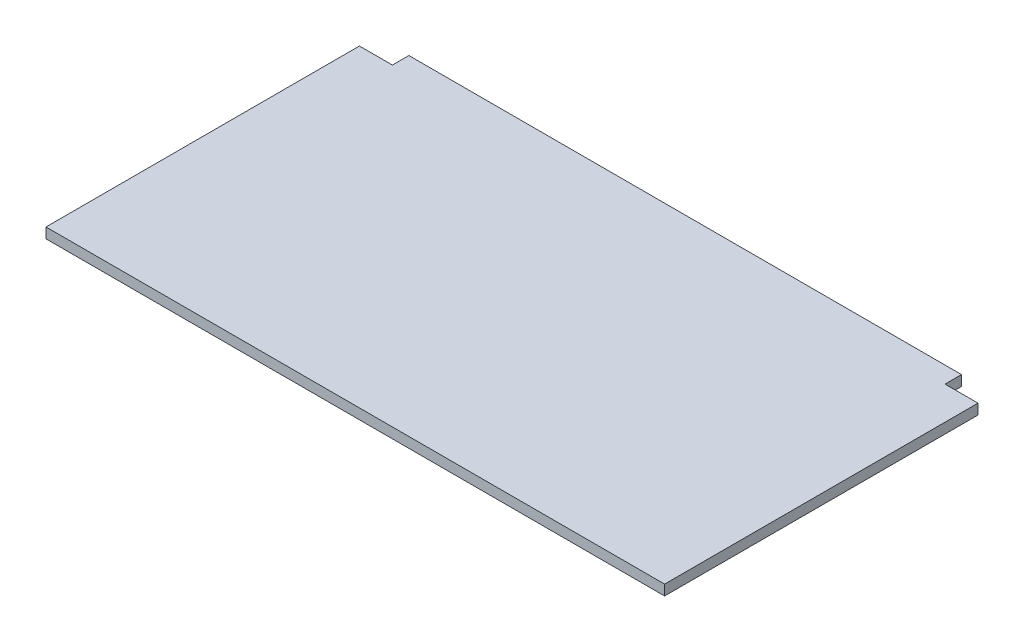
SolidWorks part; units mm, degrees
material "Cedar"
ref_plane "Front Plane" through (0, 0, 0) normal (0, 0, 1) x (1, 0, 0)
ref_plane "Top Plane" through (0, 0, 0) normal (0, 1, 0) x (1, 0, 0)
ref_plane "Right Plane" through (0, 0, 0) normal (1, 0, 0) x (0, 0, -1)
sketch "Sketch1" plane through (0, 0, 0) normal (0, 1, 0) x (1, 0, 0)
  line L1 (750, -400) -> (-750, -400)
  line L2 (750, -400) -> (750, 400)
  line L3 (750, 400) -> (-750, 400)
  line L4 (-750, -400) -> (-750, 400)
  line L5 (750, -400) -> (-750, 400) construction
  line L6 (750, 400) -> (-750, -400) construction
  point P0 (0, 0)
  dimension "D1" = 800
  dimension "D2" = 1500
extrude "Boss-Extrude1" add sketch "Sketch1" along normal blind 25
sketch "Sketch2" plane through (0, 25, 0) normal (0, 1, 0) x (1, 0, 0)
  line L0 (750, 400) -> (-750, 400) construction
  line L1 (-761.4719, 427.6992) -> (-670, 427.6992)
  line L2 (-761.4719, 427.6992) -> (-761.4719, 360)
  line L3 (-761.4719, 360) -> (-670, 360)
  line L4 (-670, 427.6992) -> (-670, 360)
  line L5 (777.3454, 416.3957) -> (670, 416.3957)
  line L6 (777.3454, 416.3957) -> (777.3454, 360)
  line L7 (777.3454, 360) -> (670, 360)
  line L8 (670, 416.3957) -> (670, 360)
  line L9 (-750, 400) -> (-750, -400) construction
  line L10 (750, -400) -> (750, 400) construction
  point P8 (-761.4719, 414.6074)
  line M5 (-750, 400) -> (-750, -400)
  line M7 (750, -400) -> (750, 400)
  line M8 (750, 400) -> (-750, 400)
  dimension "D1" = 40
  dimension "D2" = 80
  dimension "D3" = 80
extrude "Cut-Extrude1" cut sketch "Sketch2" against normal through all contours L4 L3 M8 M5 | L8 L7 M8 M7 region at (710, 25, -380) region at (-710, 25, -380)
equation "\"D3@Sketch2\"=\"D2@Sketch2\""
